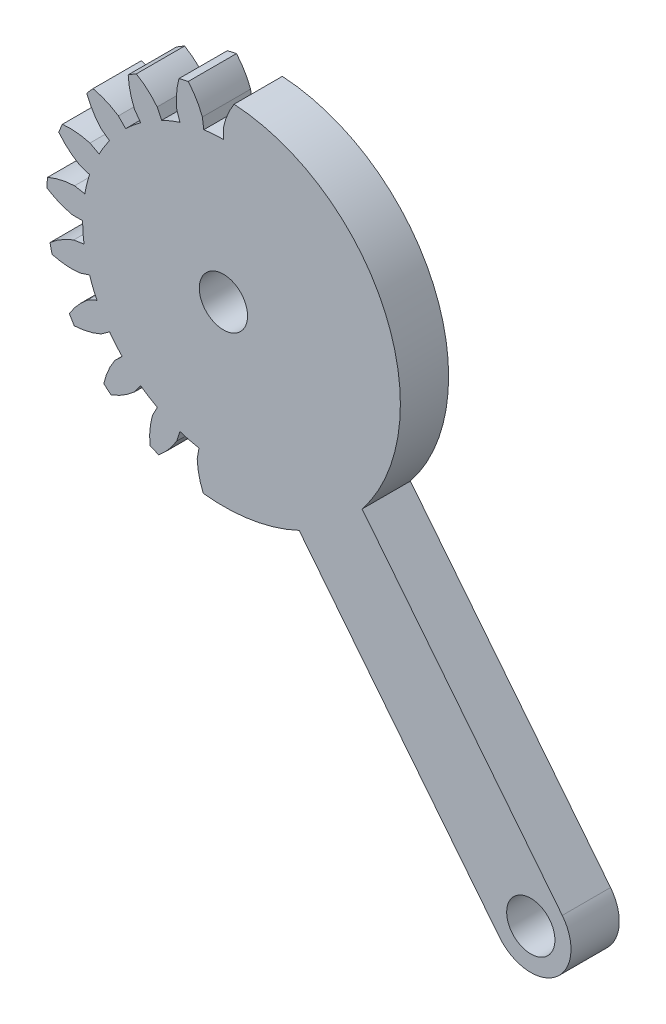
SolidWorks part; units mm, degrees
material "Plastique personnalisé"
ref_plane "Plan de face" through (0, 0, 0) normal (0, 0, 1) x (1, 0, 0)
ref_plane "Plan de dessus" through (0, 0, 0) normal (0, 1, 0) x (1, 0, 0)
ref_plane "Plan de droite" through (0, 0, 0) normal (1, 0, 0) x (0, 0, -1)
ref_axis "Axe2" through (0, 0, 0) along (0, 0, 1)
sketch "Esquisse1" plane through (0, 0, 0) normal (0, 0, 1) x (1, 0, 0)
  circle A3 centre (0, 0) radius 10
  circle A4 centre (0, 0) radius 11
  circle A5 centre (0, 0) radius 8.75
  circle A6 centre (0, 0) radius 9
  circle A7 centre (0, 0) radius 9.3969
  dimension "Pitch circle" = 20
  dimension "Addendum circle" = 22
  dimension "Root circle" = 17.5
  dimension "Clearance circle" = 18
  dimension "Base circle" = 18.7939
sketch "Involute" plane through (0, 0, 0) normal (0, 0, 1) x (1, 0, 0)
  line L0 (0, 0) -> (0, 9.3969)
  line L1 (0, 0) -> (4.6985, 8.138) construction
  line L2 (0, 0) -> (8.138, 4.6985) construction
  line L3 (0, 0) -> (9.3969, 0) construction
  line L4 (9.3969, 0) -> (9.3969, 14.7607) construction
  line L5 (8.138, 4.6985) -> (3.2178, 13.2205) construction
  line L6 (4.6985, 8.138) -> (0.4374, 10.5981) construction
  line L7 (0, 0) -> (3.0902, 9.5106)
  line L8 (0, 0) -> (1.5643, 9.8769) construction
  line L10 (0.8704, 9.962) -> (0, 0) construction
  circle A0 centre (0, 0) radius 9.3969 construction
  circle A1 centre (0, 0) radius 10 construction
  arc A5 (1.5643, 9.8769) -> (0.1723, 9.9985) centre (0, 0) ccw
  spline S0 degree 3 poles (0, 9.3969) (0.8266, 13.2451) (6.2259, 14.7657) (9.3969, 14.7607) knots 0 0 0 0 1 1 1 1
  spline S1 degree 3 poles (1.6297, 9.2545) (1.483, 13.1878) (-3.5708, 15.6216) (-6.6946, 16.1667) knots 0 0 0 0 1 1 1 1
  point P11 (0, 0)
  dimension "D2" = 9.8404
  dimension "D3" = 4.9202
  dimension "Base circle quarter circumference" = 14.7607
  dimension "Circular Pitch" = 18
  dimension "D4" = 90
  dimension "D1" = 4
sketch "Esquisse2" plane through (0, 0, 0) normal (0, 0, 1) x (1, 0, 0)
  line L1 (0, 0) -> (0, 9.3969) construction
  line L2 (0, 8.75) -> (0, 9.3969)
  line L3 (1.6297, 9.2545) -> (1.5175, 8.6174)
  arc A1 (0.6615, 10.9801) -> (0, 9.3969) centre (4.5797, 8.4132) ccw
  circle A2 centre (0, 0) radius 8.75 construction
  circle A3 centre (0, 0) radius 11 construction
  arc A4 (1.5175, 8.6174) -> (0, 8.75) centre (0, 0) ccw
  arc A5 (1.2528, 10.9284) -> (0.6615, 10.9801) centre (0, 0) ccw
  arc A7 (1.6297, 9.2545) -> (1.2503, 10.9287) centre (-3.0193, 9.0811) ccw
  spline S2 degree 3 poles (1.6297, 9.2545) (1.483, 13.1878) (-3.5708, 15.6216) (-6.6946, 16.1667) knots 0 0 0 0 1 1 1 1 construction
  spline S3 degree 3 poles (0, 9.3969) (0.8266, 13.2451) (6.2259, 14.7657) (9.3969, 14.7607) knots 0 0 0 0 1 1 1 1 construction
  point P4 (0.7616, 8.7168)
extrude "Extrusion dents" add sketch "Esquisse2" along normal blind 3 contours L3 A7 A5 A1 L2 A4 region at (0.8468, 9.6943, 0)
pattern_circular "Répétition circulaire2" count 20 over 360 about axis through (0, 0, 0) along (0, 0, 1) of bodies 191
extrude "Extrusion disque" add sketch "Esquisse1" along normal blind 3 contours A5 region at (0, 0, 0)
sketch "Esquisse3" plane through (0, 0, 3) normal (0, 0, 1) x (1, 0, 0)
  circle A2 centre (0, 0) radius 1.5
  dimension "D1" = 3
sketch "Esquisse5" plane through (0, 0, 0) normal (0, 0, -1) x (-1, 0, 0)
  line L0 (-0.9571, 10.9583) -> (0.9574, -10.9583)
  line L1 (-1.5179, 10.1093) -> (-0.2576, 10.2191) construction
  line L2 (0, -9.3969) -> (1.6297, -9.2545) construction
  circle A0 centre (0, 0) radius 11 construction
  arc A3 (-1.2503, 10.9287) -> (-1.6297, 9.2545) centre (3.0193, 9.0811) ccw construction
  arc A4 (0, 9.3969) -> (-0.6615, 10.9801) centre (-4.5797, 8.4132) ccw construction
  arc A5 (-0.9571, 10.9583) -> (0.9574, -10.9583) centre (0, 0) ccw
  point P4 (-0.8878, 10.1642)
  point P17 (0.8148, -9.3257)
extrude "Boss.-Extru.1" add sketch "Esquisse5" against normal blind 3
sketch "Esquisse6" plane through (0, 0, 0) normal (0, 0, -1) x (-1, 0, 0)
  line L0 (0, 0) -> (-19.1076, -24.0444) construction
  line L1 (1.2503, -10.9287) -> (0, 0) construction
  line L2 (-8.6218, -6.8311) -> (-21.0649, -22.489)
  line L4 (-4.7073, -9.9419) -> (-17.1504, -25.5998)
  circle A0 centre (0, 0) radius 11 construction
  arc A2 (-21.0649, -22.489) -> (-17.1504, -25.5998) centre (-19.1076, -24.0444) ccw
  circle A3 centre (-19.1076, -24.0444) radius 1.5
  arc A4 (-8.6218, -6.8311) -> (-4.7073, -9.9419) centre (0, 0) ccw
  dimension "D4" = 3
  dimension "D1" = 45
  dimension "D2" = 20
  dimension "D3" = 2.5
extrude "Boss.-Extru.2" add sketch "Esquisse6" against normal blind 3
extrude "Enlèv. mat.-Extru.1" cut sketch "Esquisse3" against normal through all contours A2
equation "\"Module\"= 1"
equation "\"Nb of teeth\"= 20"
equation "\"Pressure angle\"= 20deg"
equation "\"Pitch circle@Esquisse1\"= \"Module\" * \"Nb of teeth\""
equation "\"Addendum circle@Esquisse1\" = \"Pitch circle@Esquisse1\" + ( \"Module\" * 2 )"
equation "\"Clearance circle@Esquisse1\"= \"Pitch circle@Esquisse1\" - ( \"Module\" * 2 )"
equation "\"Root circle@Esquisse1\"= \"Pitch circle@Esquisse1\" - ( ( \"Module\" * 1.25 ) * 2 )"
equation "\"Base circle@Esquisse1\"= \"Pitch circle@Esquisse1\" * cos ( \"Pressure angle\" )"
equation "\"D2@Involute\" = \"Base circle quarter circumference@Involute\" / 3 * 2"
equation "\"Base circle quarter circumference@Involute\" = \"Base circle@Esquisse1\" * pI / 4"
equation "\"D3@Involute\" = \"Base circle quarter circumference@Involute\" / 3"
equation "\"Circular Pitch@Involute\"=360 / \"Nb of teeth\""
equation "\"D1@Répétition circulaire2\"= \"Nb of teeth\""
equation "\"D1@Extrusion disque\" = \"D1@Extrusion dents\""
